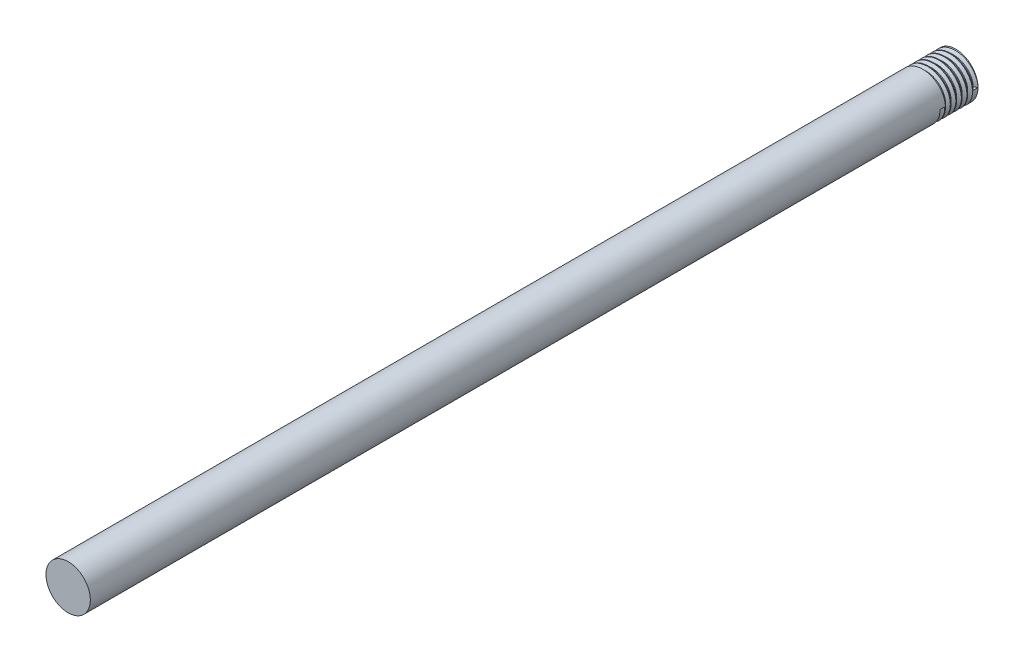
SolidWorks part; units mm, degrees
ref_plane "Ebene vorne" through (0, 0, 0) normal (0, 0, 1) x (1, 0, 0)
ref_plane "Ebene oben" through (0, 0, 0) normal (0, 1, 0) x (1, 0, 0)
ref_plane "Ebene rechts" through (0, 0, 0) normal (1, 0, 0) x (0, 0, -1)
sketch "Sketch1" plane through (0, 0, 0) normal (0, 0, 1) x (1, 0, 0)
  circle A0 centre (0, 0) radius 1
  dimension "D1" = 2
extrude "Boss-Extrude1" add sketch "Sketch1" along normal blind 40
thread "Thread1" pitch 0.25 method cut profile "Thread Profile1" start angle 0, offset 0, length 1.5, pitch 0.25, diameter 2
ref_plane "Plane1" through (1, 0, 0) normal (0, -1, 0) x (1, 0, 0)
sketch "Thread Profile1" plane through (1, 0, 0) normal (0, -1, 0) x (1, 0, 0)
  line L0 (0, 0) -> (0, 0.25) construction
  line L11 (0, 0) -> (0, 0.2187)
  line L12 (0, 0.2187) -> (-0.1353, 0.1406)
  line L13 (-0.1353, 0.1406) -> (-0.1353, 0.0781)
  line L15 (-0.1353, 0.0781) -> (0, 0)
  line L17 (-0.1353, 0.1094) -> (0, 0.1094) construction
  point P2 (0, 0)
  dimension "Pitch" = 0.25
  dimension "Profile_Angle" = 60
  dimension "Profile_Land" = 0.0625
  dimension "Profile_Height" = 0.1353
